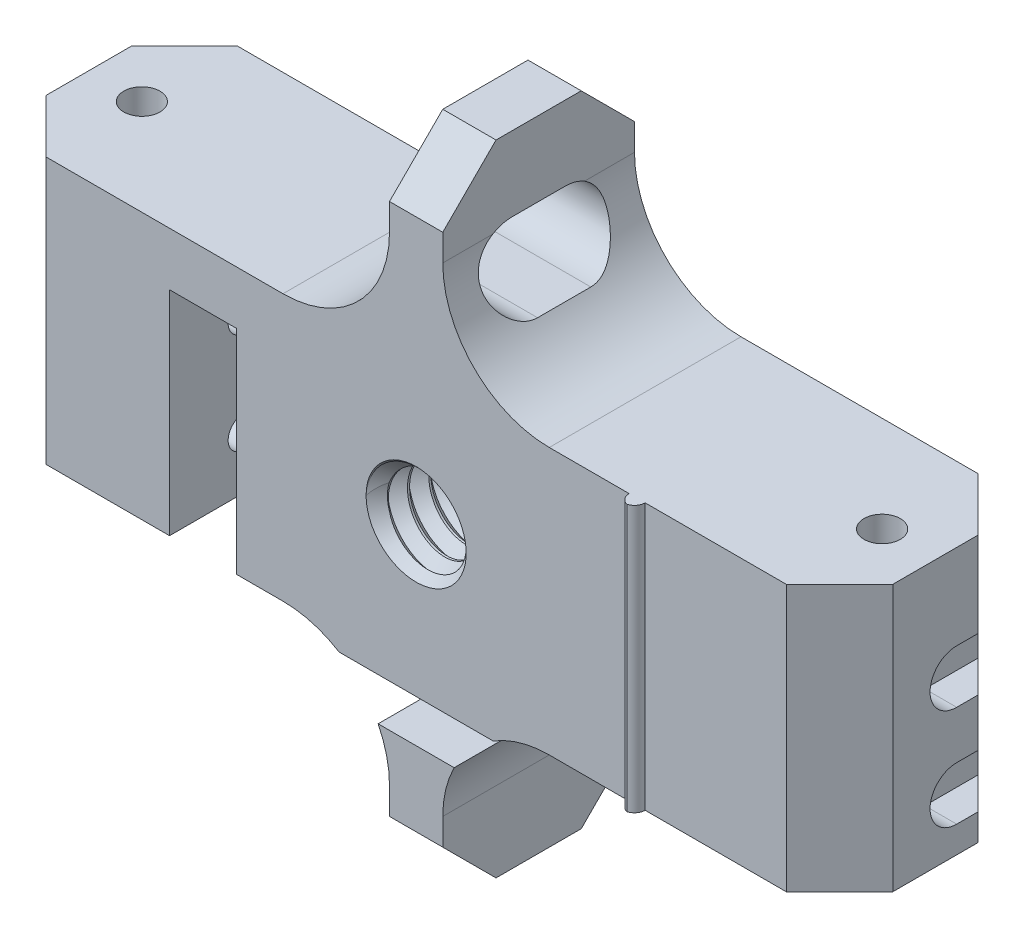
SolidWorks part; units mm, degrees
ref_plane "Ön Düzlem" through (0, 0, 0) normal (0, 0, 1) x (1, 0, 0)
ref_plane "Üst Düzlem" through (0, 0, 0) normal (0, 1, 0) x (1, 0, 0)
ref_plane "Sağ Düzlem" through (0, 0, 0) normal (1, 0, 0) x (0, 0, -1)
sketch "Çizim1" plane through (0, 0, 0) normal (0, 0, 1) x (1, 0, 0)
  line L0 (39.75, -28.7334) -> (39.75, 65.8801) construction
  line L1 (0, 0) -> (27.25, 0)
  line L2 (0, 0) -> (0, 25)
  line L3 (0, 25) -> (27.25, 25)
  line L4 (79.5, 0) -> (79.5, 25)
  line L5 (37.25, -10) -> (37.25, -17.5)
  line L6 (37.25, -17.5) -> (42.25, -17.5)
  line L7 (42.25, -17.5) -> (42.25, -10)
  line L8 (37.25, 35) -> (37.25, 42.5)
  line L9 (37.25, 42.5) -> (42.25, 42.5)
  line L10 (42.25, 42.5) -> (42.25, 35)
  line L11 (52.25, 25) -> (79.5, 25)
  line L12 (52.25, 0) -> (79.5, 0)
  arc A0 (27.25, 25) -> (37.25, 35) centre (27.25, 35) ccw
  arc A1 (52.25, 25) -> (42.25, 35) centre (52.25, 35) cw
  arc A2 (27.25, 0) -> (37.25, -10) centre (27.25, -10) cw
  arc A3 (52.25, 0) -> (42.25, -10) centre (52.25, -10) ccw
  point P19 (42.25, 25)
  point P22 (37.25, 0)
  point P25 (42.25, 0)
  dimension "D2" = 10
  dimension "D4" = 10
  dimension "D7" = 10
  dimension "D8" = 10
  dimension "D1" = 25
  dimension "D3" = 5
  dimension "D5" = 17.5
  dimension "D6" = 79.5
  dimension "D9" = 17.5
extrude "Yükseklik-Ekstrüzyon1" add sketch "Çizim1" along normal blind 18
chamfer "Pah1" distance 5 angle 45 2 edges at (79.5, 12.5, 0) (79.5, 12.5, 18)
chamfer "Pah2" distance 5 angle 45 2 edges at (0, 12.5, 0) (0, 12.5, 18)
chamfer "Pah3" distance 5 angle 45 4 edges at (39.75, -17.5, 0) (39.75, -17.5, 18) (39.75, 42.5, 0) (39.75, 42.5, 18)
sketch "Çizim2" plane through (42.25, 0, 0) normal (1, 0, 0) x (0, 0, -1)
  line L0 (-24.2744, -3.5) -> (5.207, -3.5) construction
  line L1 (-13, 0) -> (-18, 0) construction
  line L2 (-12, -5.5) -> (-20.654, -5.5)
  line L3 (-20.654, -5.5) -> (-20.654, -1.5)
  line L4 (-20.654, -1.5) -> (-12, -1.5)
  line L5 (-18, 0) -> (-18, -10) construction
  arc A0 (-12, -5.5) -> (-12, -1.5) centre (-12, -3.5) ccw
  dimension "D2" = 4
  dimension "D1" = 3.5
  dimension "D3" = 8.654
  dimension "D4" = 6
extrude "Kes-Ekstrüzyon1" cut sketch "Çizim2" against normal blind 18 and the other way blind 18
sketch "Çizim3" plane through (0, 0, 18) normal (0, 0, 1) x (1, 0, 0)
  line L0 (39.75, 42.5) -> (39.75, -17.5) construction
  line L1 (37.25, 42.5) -> (42.25, 42.5) construction
  line L2 (42.25, -17.5) -> (37.25, -17.5) construction
  line L3 (19.75, 36.1927) -> (19.75, -8.4053) construction
  line L4 (5, 0) -> (27.25, 0) construction
  line L5 (16.6, 0) -> (22.9, 0)
  line L6 (16.6, 0) -> (16.6, 20)
  line L7 (16.6, 20) -> (22.9, 20)
  line L8 (22.9, 0) -> (22.9, 20)
  dimension "D1" = 20
  dimension "D2" = 20
  dimension "D3" = 6.3
extrude "Kes-Ekstrüzyon2" cut sketch "Çizim3" against normal blind 15.5
sketch "Çizim4" plane through (0, 0, 0) normal (0, 0, -1) x (-1, 0, 0)
  line L0 (-39.75, -17.5) -> (-39.75, 42.5) construction
  line L1 (-37.25, -17.5) -> (-42.25, -17.5) construction
  line L2 (-42.25, 42.5) -> (-37.25, 42.5) construction
  line L3 (-59.75, -12.5466) -> (-59.75, 39.3783) construction
  line L4 (-52.25, 0) -> (-74.5, 0) construction
  line L5 (-56.6, 0) -> (-62.9, 0)
  line L6 (-56.6, 0) -> (-56.6, 20)
  line L7 (-56.6, 20) -> (-62.9, 20)
  line L8 (-62.9, 0) -> (-62.9, 20)
  dimension "D1" = 20
  dimension "D2" = 6.3
  dimension "D3" = 20
extrude "Kes-Ekstrüzyon3" cut sketch "Çizim4" against normal blind 15.5
sketch "Çizim5" plane through (0, 0, 0) normal (-1, 0, 0) x (0, 0, 1)
  line L0 (11, 53.0109) -> (11, -25.9673) construction
  line L1 (18, 25) -> (18, 0) construction
  line L2 (18, 0) -> (0, 0) construction
  circle A0 centre (11, 5) radius 1.5
  circle A1 centre (11, 14.5) radius 1.5
  dimension "D2" = 3
  dimension "D3" = 3
  dimension "D1" = 7
  dimension "D4" = 9.5
  dimension "D5" = 5
extrude "Kes-Ekstrüzyon4" cut sketch "Çizim5" against normal blind 28
sketch "Çizim6" plane through (79.5, 0, 0) normal (1, 0, 0) x (0, 0, -1)
  line L0 (-7, -32.2784) -> (-7, 54.0935) construction
  line L1 (0, 25) -> (0, 0) construction
  line L2 (-13, 0) -> (-5, 0) construction
  circle A0 centre (-7, 5) radius 1.5
  circle A1 centre (-7, 14.5) radius 1.5
  dimension "D3" = 3
  dimension "D4" = 3
  dimension "D1" = 7
  dimension "D2" = 9.5
  dimension "D5" = 5
extrude "Kes-Ekstrüzyon6" cut sketch "Çizim6" against normal blind 28
sketch "Çizim7" plane through (0, 0, 0) normal (0, -1, 0) x (1, 0, 0)
  line L0 (-17.1125, 9) -> (94.6238, 9) construction
  line L2 (0, 13) -> (0, 5) construction
  line L3 (5, 18) -> (16.6, 18) construction
  line L4 (5, 0) -> (27.25, 0) construction
  circle A0 centre (5, 9) radius 1.7
  dimension "D2" = 3.4
  dimension "D4" = 5
extrude "Kes-Ekstrüzyon13" cut sketch "Çizim7" against normal blind 28
sketch "Çizim8" plane through (0, 0, 0) normal (0, -1, 0) x (1, 0, 0)
  line L0 (-12.4138, 9) -> (90.6396, 9) construction
  line L2 (79.5, 13) -> (79.5, 5) construction
  line L3 (52.25, 18) -> (74.5, 18) construction
  line L4 (62.9, 0) -> (74.5, 0) construction
  circle A0 centre (74.5, 9) radius 1.7
  dimension "D3" = 3.4
  dimension "D2" = 5
extrude "Kes-Ekstrüzyon14" cut sketch "Çizim8" against normal blind 28
sketch "Çizim9" plane through (0, 0, 0) normal (-1, 0, 0) x (0, 0, 1)
  line L0 (11, 17) -> (21, 17)
  line L1 (21, 17) -> (21, 12)
  line L2 (21, 12) -> (11, 12)
  line L3 (11, 7.5) -> (21, 7.5)
  line L4 (21, 7.5) -> (21, 2.5)
  line L5 (21, 2.5) -> (11, 2.5)
  arc A0 (11, 17) -> (11, 12) centre (11, 14.5) ccw
  arc A1 (11, 7.5) -> (11, 2.5) centre (11, 5) ccw
  dimension "D1" = 5
  dimension "D2" = 5
  dimension "D3" = 10
extrude "Kes-Ekstrüzyon15" cut sketch "Çizim9" against normal blind 3
sketch "Çizim10" plane through (79.5, 0, 0) normal (1, 0, 0) x (0, 0, -1)
  line L0 (-7, 2.5) -> (3, 2.5)
  line L1 (3, 2.5) -> (3, 7.5)
  line L2 (3, 7.5) -> (-7, 7.5)
  line L3 (-7, 12) -> (3, 12)
  line L4 (3, 12) -> (3, 17)
  line L5 (3, 17) -> (-7, 17)
  arc A0 (-7, 7.5) -> (-7, 2.5) centre (-7, 5) ccw
  arc A1 (-7, 17) -> (-7, 12) centre (-7, 14.5) ccw
  dimension "D1" = 5
  dimension "D2" = 5
  dimension "D3" = 10
  dimension "D4" = 10
extrude "Kes-Ekstrüzyon16" cut sketch "Çizim10" against normal blind 3
sketch "Çizim11" plane through (0, 0, 18) normal (0, 0, 1) x (1, 0, 0)
  line L0 (74.5, 12.5) -> (-16.2365, 12.5) construction
  line L1 (74.5, 0) -> (74.5, 25) construction
  line L2 (39.75, 42.5) -> (39.75, -17.5) construction
  line L3 (37.25, 42.5) -> (42.25, 42.5) construction
  line L4 (42.25, -17.5) -> (37.25, -17.5) construction
  circle A0 centre (39.75, 12.5) radius 3.7
  dimension "D1" = 7.4
extrude "Kes-Ekstrüzyon17" cut sketch "Çizim11" against normal blind 20
sketch "Çizim13" plane through (0, 0, 18) normal (0, 0, 1) x (1, 0, 0)
  line L0 (60.5, -11.352) -> (60.5, 31.3347) construction
  line L1 (5, 25) -> (5, 0) construction
  line L3 (52.25, 0) -> (74.5, 0) construction
  line L4 (61.25, 0) -> (59.75, 0)
  line L5 (61.25, 0) -> (61.25, 25)
  line L6 (61.25, 25) -> (59.75, 25)
  line L7 (59.75, 0) -> (59.75, 25)
  line L8 (74.5, 25) -> (52.25, 25) construction
  dimension "D1" = 55.5
  dimension "D2" = 1.5
extrude "Yükseklik-Ekstrüzyon2" add sketch "Çizim13" along normal blind 1
fillet "Radyus1" radius 1 2 edges at (59.75, 12.5, 19) (61.25, 12.5, 19)
sketch "Çizim15" plane through (0, 0, 0) normal (-1, 0, 0) x (0, 0, 1)
  line L0 (11.5, 32) -> (6.5, 32) construction
  line L1 (11.5, 28.5) -> (6.5, 28.5)
  line L2 (11.5, 35.5) -> (6.5, 35.5)
  line L3 (18, 25) -> (18, 35) construction
  line L5 (13, 42.5) -> (5, 42.5) construction
  arc A0 (11.5, 28.5) -> (11.5, 35.5) centre (11.5, 32) ccw
  arc A1 (6.5, 35.5) -> (6.5, 28.5) centre (6.5, 32) ccw
  point P2 (9, 32)
  point P9 (9, 42.5)
  dimension "D1" = 5
  dimension "D2" = 6.5
  dimension "D3" = 7
  dimension "D4" = 7
extrude "Kes-Ekstrüzyon19" cut sketch "Çizim15" against normal blind 52
chamfer "Pah4" distance 1 angle 45 2 edges at (43.45, 12.5, 0) (43.45, 12.5, 18)
ref_plane "Düzlem1" through (0, 12.5, 0) normal (0, -1, 0) x (-1, 0, 0)
sketch "Çizim16" plane through (0, 12.5, 0) normal (0, -1, 0) x (-1, 0, 0)
  line L0 (-39.75, 11.5133) -> (-39.75, -24.7013) construction
  line L1 (-79.5, -13) -> (-79.5, -5) construction
  line L2 (0, -13) -> (0, -5) construction
sketch "Çizim17" plane through (0, 0, 18) normal (0, 0, 1) x (1, 0, 0)
  circle A0 centre (39.75, 12.5) radius 3.7
  dimension "D1" = 7.4
curve "Helis/Spiral1" pitch 2 height 20 radius 3.7 centre (39.75, 12.5, 18) axis (0, 0, -1) start towards (-1, 0, 0)
sketch "Çizim19" plane through (0, 12.5, 0) normal (0, -1, 0) x (-1, 0, 0)
  line L0 (-36.05, -17.1) -> (-36.05, -18.9)
  line L1 (-36.05, -18.9) -> (-35.05, -18)
  line L2 (-35.05, -18) -> (-36.05, -17.1)
  line L3 (-36.05, -18) -> (-34.05, -18) construction
  line L4 (-32.5178, -18) -> (-46.9822, -18) construction
  line L5 (-37.25, -18) -> (-42.25, -18) construction
  spline S0 degree 3 poles (-36.05, -18) (-36.05, -17.9586) (-36.2427, -17.8749) (-37.0656, -17.75) (-38.2972, -17.625) (-39.75, -17.5) (-41.2028, -17.375) (-42.4344, -17.25) (-43.2573, -17.125) (-43.5463, -17) (-43.2573, -16.875) (-42.4344, -16.75) (-41.2028, -16.625) (-39.75, -16.5) (-38.2972, -16.375) (-37.0656, -16.25) (-36.2427, -16.125) (-35.9537, -16) (-36.2427, -15.875) (-37.0656, -15.75) (-38.2972, -15.625) (-39.75, -15.5) (-41.2028, -15.375) (-42.4344, -15.25) (-43.2573, -15.125) (-43.5463, -15) (-43.2573, -14.875) (-42.4344, -14.75) (-41.2028, -14.625) (-39.75, -14.5) (-38.2972, -14.375) (-37.0656, -14.25) (-36.2427, -14.125) (-35.9537, -14) (-36.2427, -13.875) (-37.0656, -13.75) (-38.2972, -13.625) (-39.75, -13.5) (-41.2028, -13.375) (-42.4344, -13.25) (-43.2573, -13.125) (-43.5463, -13) (-43.2573, -12.875) (-42.4344, -12.75) (-41.2028, -12.625) (-39.75, -12.5) (-38.2972, -12.375) (-37.0656, -12.25) (-36.2427, -12.125) (-35.9537, -12) (-36.2427, -11.875) (-37.0656, -11.75) (-38.2972, -11.625) (-39.75, -11.5) (-41.2028, -11.375) (-42.4344, -11.25) (-43.2573, -11.125) (-43.5463, -11) (-43.2573, -10.875) (-42.4344, -10.75) (-41.2028, -10.625) (-39.75, -10.5) (-38.2972, -10.375) (-37.0656, -10.25) (-36.2427, -10.125) (-35.9537, -10) (-36.2427, -9.875) (-37.0656, -9.75) (-38.2972, -9.625) (-39.75, -9.5) (-41.2028, -9.375) (-42.4344, -9.25) (-43.2573, -9.125) (-43.5463, -9) (-43.2573, -8.875) (-42.4344, -8.75) (-41.2028, -8.625) (-39.75, -8.5) (-38.2972, -8.375) (-37.0656, -8.25) (-36.2427, -8.125) (-35.9537, -8) (-36.2427, -7.875) (-37.0656, -7.75) (-38.2972, -7.625) (-39.75, -7.5) (-41.2028, -7.375) (-42.4344, -7.25) (-43.2573, -7.125) (-43.5463, -7) (-43.2573, -6.875) (-42.4344, -6.75) (-41.2028, -6.625) (-39.75, -6.5) (-38.2972, -6.375) (-37.0656, -6.25) (-36.2427, -6.125) (-35.9537, -6) (-36.2427, -5.875) (-37.0656, -5.75) (-38.2972, -5.625) (-39.75, -5.5) (-41.2028, -5.375) (-42.4344, -5.25) (-43.2573, -5.125) (-43.5463, -5) (-43.2573, -4.875) (-42.4344, -4.75) (-41.2028, -4.625) (-39.75, -4.5) (-38.2972, -4.375) (-37.0656, -4.25) (-36.2427, -4.125) (-35.9537, -4) (-36.2427, -3.875) (-37.0656, -3.75) (-38.2972, -3.625) (-39.75, -3.5) (-41.2028, -3.375) (-42.4344, -3.25) (-43.2573, -3.125) (-43.5463, -3) (-43.2573, -2.875) (-42.4344, -2.75) (-41.2028, -2.625) (-39.75, -2.5) (-38.2972, -2.375) (-37.0656, -2.25) (-36.2427, -2.125) (-35.9537, -2) (-36.2427, -1.875) (-37.0656, -1.75) (-38.2972, -1.625) (-39.75, -1.5) (-41.2028, -1.375) (-42.4344, -1.25) (-43.2573, -1.125) (-43.5463, -1) (-43.2573, -0.875) (-42.4344, -0.75) (-41.2028, -0.625) (-39.75, -0.5) (-38.2972, -0.375) (-37.0656, -0.25) (-36.2427, -0.125) (-35.9537, 0) (-36.2427, 0.125) (-37.0656, 0.25) (-38.2972, 0.375) (-39.75, 0.5) (-41.2028, 0.625) (-42.4344, 0.75) (-43.2573, 0.875) (-43.5463, 1) (-43.2573, 1.125) (-42.4344, 1.25) (-41.2028, 1.375) (-39.75, 1.5) (-38.2972, 1.625) (-37.0656, 1.75) (-36.2427, 1.8749) (-36.05, 1.9586) (-36.05, 2) knots 0 0 0 0 0.00625 0.0125 0.01875 0.025 0.03125 0.0375 0.04375 0.05 0.05625 0.0625 0.06875 0.075 0.08125 0.0875 0.09375 0.1 0.10625 0.1125 0.11875 0.125 0.13125 0.1375 0.14375 0.15 0.15625 0.1625 0.16875 0.175 0.18125 0.1875 0.19375 0.2 0.20625 0.2125 0.21875 0.225 0.23125 0.2375 0.24375 0.25 0.25625 0.2625 0.26875 0.275 0.28125 0.2875 0.29375 0.3 0.30625 0.3125 0.31875 0.325 0.33125 0.3375 0.34375 0.35 0.35625 0.3625 0.36875 0.375 0.38125 0.3875 0.39375 0.4 0.40625 0.4125 0.41875 0.425 0.43125 0.4375 0.44375 0.45 0.45625 0.4625 0.46875 0.475 0.48125 0.4875 0.49375 0.5 0.50625 0.5125 0.51875 0.525 0.53125 0.5375 0.54375 0.55 0.55625 0.5625 0.56875 0.575 0.58125 0.5875 0.59375 0.6 0.60625 0.6125 0.61875 0.625 0.63125 0.6375 0.64375 0.65 0.65625 0.6625 0.66875 0.675 0.68125 0.6875 0.69375 0.7 0.70625 0.7125 0.71875 0.725 0.73125 0.7375 0.74375 0.75 0.75625 0.7625 0.76875 0.775 0.78125 0.7875 0.79375 0.8 0.80625 0.8125 0.81875 0.825 0.83125 0.8375 0.84375 0.85 0.85625 0.8625 0.86875 0.875 0.88125 0.8875 0.89375 0.9 0.90625 0.9125 0.91875 0.925 0.93125 0.9375 0.94375 0.95 0.95625 0.9625 0.96875 0.975 0.98125 0.9875 0.99375 1 1 1 1 construction
  dimension "D1" = 1.8
  dimension "D2" = 1
sweep "Kes-Süpür3" cut profiles "Çizim19" path "Helis/Spiral1" align with end faces yes
